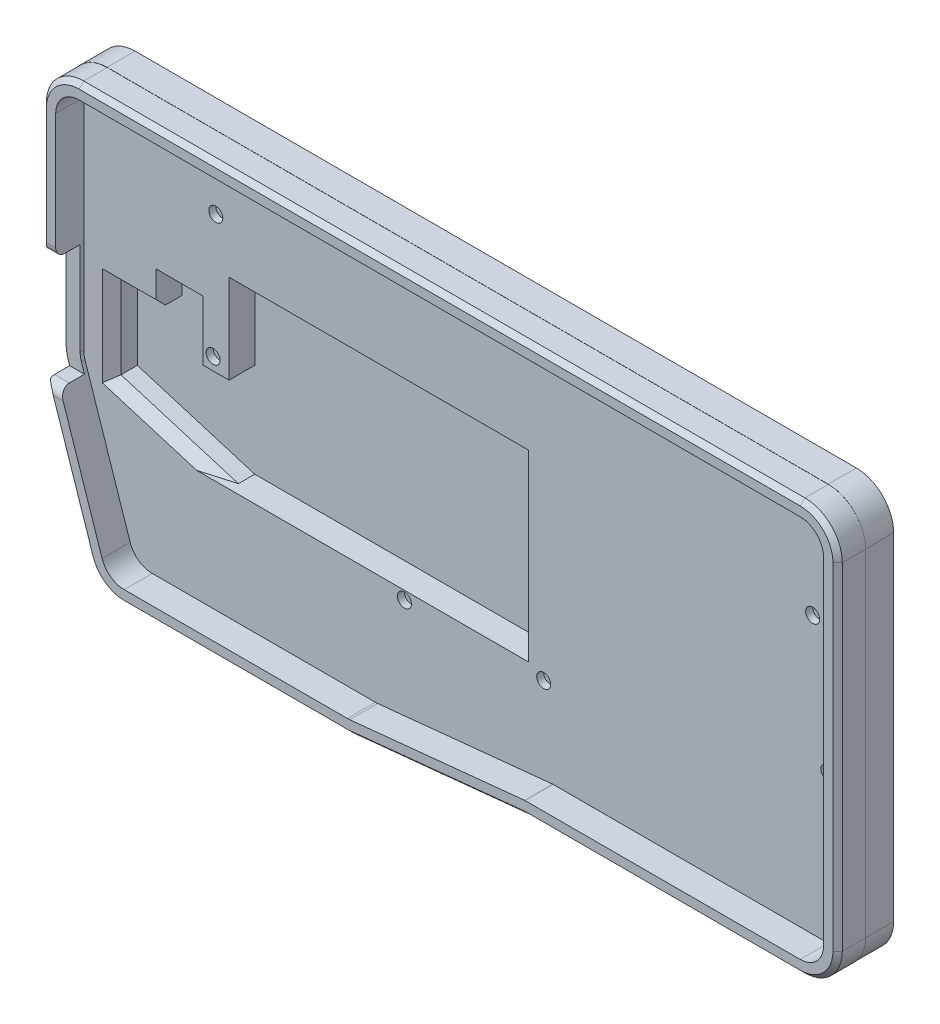
SolidWorks part; units mm, degrees
ref_plane "Front Plane" through (0, 0, 0) normal (0, 0, 1) x (1, 0, 0)
ref_plane "Top Plane" through (0, 0, 0) normal (0, 1, 0) x (1, 0, 0)
ref_plane "Right Plane" through (0, 0, 0) normal (1, 0, 0) x (0, 0, -1)
sketch "Sketch3" plane through (0, 0, 0) normal (0, 0, 1) x (1, 0, 0)
  line B0 (-83.6984, 57.4446) -> (70.5516, 57.3483)
  line B1 (78.5466, 49.3483) -> (78.5466, -22.6536)
  line B2 (70.5466, -30.6536) -> (11.7979, -30.6536)
  line B3 (11.7979, -30.6536) -> (-25.502, -34.4132)
  line B4 (-26.3043, -34.4536) -> (-74.0412, -34.4536)
  line B5 (-81.6306, -28.9834) -> (-91.2929, 0.0035)
  line B6 (-91.7034, 2.5333) -> (-91.7034, 49.4446)
  line B7 (-83.7003, 54.4446) -> (70.5497, 54.3483)
  line B8 (75.5466, 49.3483) -> (75.5466, -22.6536)
  line B9 (70.5466, -27.6536) -> (11.6974, -27.6536)
  line B10 (11.5971, -27.6586) -> (-25.8028, -31.4283)
  line B11 (-26.3043, -31.4536) -> (-74.0412, -31.4536)
  line B12 (-78.7846, -28.0347) -> (-88.4469, 0.9521)
  line B13 (-88.7034, 2.5333) -> (-88.7034, 49.4446)
  arc B14 (78.5466, 49.3483) -> (70.5516, 57.3483) centre (70.5466, 49.3483) ccw
  arc B15 (70.5466, -30.6536) -> (78.5466, -22.6536) centre (70.5466, -22.6536) ccw
  arc B16 (-26.3043, -34.4536) -> (-25.502, -34.4132) centre (-26.3043, -26.4536) ccw
  arc B17 (-81.6306, -28.9834) -> (-74.0412, -34.4536) centre (-74.0412, -26.4536) ccw
  arc B18 (-91.7034, 2.5333) -> (-91.2929, 0.0035) centre (-83.7034, 2.5333) ccw
  arc B19 (-83.6984, 57.4446) -> (-91.7034, 49.4446) centre (-83.7034, 49.4446) ccw
  arc B20 (75.5466, 49.3483) -> (70.5497, 54.3483) centre (70.5466, 49.3483) ccw
  arc B21 (70.5466, -27.6536) -> (75.5466, -22.6536) centre (70.5466, -22.6536) ccw
  arc B22 (11.6974, -27.6536) -> (11.5971, -27.6586) centre (11.6974, -28.6536) ccw
  arc B23 (-26.3043, -31.4536) -> (-25.8028, -31.4283) centre (-26.3043, -26.4536) ccw
  arc B24 (-78.7846, -28.0347) -> (-74.0412, -31.4536) centre (-74.0412, -26.4536) ccw
  arc B25 (-88.7034, 2.5333) -> (-88.4469, 0.9521) centre (-83.7034, 2.5333) ccw
  arc B26 (-83.7003, 54.4446) -> (-88.7034, 49.4446) centre (-83.7034, 49.4446) ccw
sketch_block_instance "wall_outline (2)-1"
sketch_block "wall_outline (2)"
extrude "Boss-Extrude1" add sketch "Sketch3" along normal blind 6
sketch "Sketch4" plane through (0, 0, 0) normal (0, 0, 1) x (1, 0, 0)
  line B0 (-83.7091, 57.4792) -> (70.5409, 57.3829)
  line B1 (78.5359, 49.3829) -> (78.5359, -22.619)
  line B2 (70.5359, -30.619) -> (11.7872, -30.619)
  line B3 (11.7872, -30.619) -> (-25.5126, -34.3786)
  line B4 (-26.3149, -34.419) -> (-74.0518, -34.419)
  line B5 (-81.6413, -28.9488) -> (-91.3036, 0.038)
  line B6 (-91.7141, 2.5679) -> (-91.7141, 49.4792)
  line B7 (-83.711, 54.4792) -> (70.539, 54.3829)
  line B8 (75.5359, 49.3829) -> (75.5359, -22.619)
  line B9 (70.5359, -27.619) -> (11.6867, -27.619)
  line B10 (11.5864, -27.624) -> (-25.8135, -31.3938)
  line B11 (-26.3149, -31.419) -> (-74.0518, -31.419)
  line B12 (-78.7953, -28.0001) -> (-88.4575, 0.9867)
  line B13 (-88.7141, 2.5679) -> (-88.7141, 49.4792)
  arc B14 (78.5359, 49.3829) -> (70.5409, 57.3829) centre (70.5359, 49.3829) ccw
  arc B15 (70.5359, -30.619) -> (78.5359, -22.619) centre (70.5359, -22.619) ccw
  arc B16 (-26.3149, -34.419) -> (-25.5126, -34.3786) centre (-26.3149, -26.419) ccw
  arc B17 (-81.6413, -28.9488) -> (-74.0518, -34.419) centre (-74.0518, -26.419) ccw
  arc B18 (-91.7141, 2.5679) -> (-91.3036, 0.038) centre (-83.7141, 2.5679) ccw
  arc B19 (-83.7091, 57.4792) -> (-91.7141, 49.4792) centre (-83.7141, 49.4792) ccw
  arc B20 (75.5359, 49.3829) -> (70.539, 54.3829) centre (70.5359, 49.3829) ccw
  arc B21 (70.5359, -27.619) -> (75.5359, -22.619) centre (70.5359, -22.619) ccw
  arc B22 (11.6867, -27.619) -> (11.5864, -27.624) centre (11.6867, -28.619) ccw
  arc B23 (-26.3149, -31.419) -> (-25.8135, -31.3938) centre (-26.3149, -26.419) ccw
  arc B24 (-78.7953, -28.0001) -> (-74.0518, -31.419) centre (-74.0518, -26.419) ccw
  arc B25 (-88.7141, 2.5679) -> (-88.4575, 0.9867) centre (-83.7141, 2.5679) ccw
  arc B26 (-83.711, 54.4792) -> (-88.7141, 49.4792) centre (-83.7141, 49.4792) ccw
  circle B27 centre (-60.4641, 41.881) radius 1
  circle B28 centre (-61.0341, 15.281) radius 1
  circle B29 centre (-20.1141, -9.419) radius 1
  circle B30 centre (9.6859, -9.419) radius 1
  circle B31 centre (70.4859, 3.881) radius 1
  circle B32 centre (67.2159, 31.431) radius 1
sketch_block_instance "wall_outline (3)-1"
sketch_block "wall_outline (3)"
extrude "Boss-Extrude2" add sketch "Sketch4" against normal blind 6 contours B7 B26 B13 B25 B12 B24 B11 B23 B10 B22 B9 B21 B8 B20 B32 B31 B30 B29 B28 B27 | B0 B19 B6 B18 B5 B17 B4 B16 B3 B2 B15 B1 B14 B26 B7 B20 B8 B21 B9 B22 B10 B23 B11 B24 B12 B25 B13 region at (-6.5853, 55.4963, 0) region at (-6.5032, 12.8796, 0)
sketch "Sketch5" plane through (0, 0, 0) normal (0, 0, 1) x (1, 0, 0)
  line L1 (-57.625, 35.0163) -> (6.3958, 35.0163)
  line L2 (-57.625, 35.0163) -> (-57.625, -7.6057)
  line L3 (-57.625, -7.6057) -> (6.3958, -7.6057)
  line L4 (6.3958, 35.0163) -> (6.3958, -7.6057)
  line L5 (-76.0419, 12.5652) -> (-50.0828, 12.5652)
  line L6 (-76.0419, 12.5652) -> (-76.0419, -1.6421)
  line L7 (-76.0419, -1.6421) -> (-50.0828, -1.6421)
  line L8 (-50.0828, 12.5652) -> (-50.0828, -1.6421)
extrude "Cut-Extrude2" cut sketch "Sketch5" against normal blind 5.5 contours L6 L7 L2 L5 | L8 L5 L2 L7 | L5 L8 L7 L2 L3 L4 L1 region at (-24.4603, 14.0423, 0) region at (-53.8539, 5.4615, 0) region at (-66.8334, 5.4615, 0)
sketch "Sketch6" plane through (0, 0, -6) normal (0, 0, -1) x (-1, 0, 0)
  circle A0 centre (-67.2159, 31.431) radius 1
  circle A1 centre (-70.4859, 3.881) radius 1
  circle A2 centre (-9.6859, -9.419) radius 1
  circle A3 centre (20.1141, -9.419) radius 1
  circle A4 centre (61.0341, 15.281) radius 1
  circle A5 centre (60.4641, 41.881) radius 1
extrude "Boss-Extrude3" add sketch "Sketch6" against normal blind 5.5
sketch "Sketch7" plane through (0, 0, 0) normal (0, 0, 1) x (1, 0, 0)
  circle A0 centre (-60.4641, 41.881) radius 1.5
  circle A1 centre (-61.0341, 15.281) radius 1.5
  circle A2 centre (-20.1141, -9.419) radius 1.5
  circle A3 centre (9.6859, -9.419) radius 1.5
  circle A7 centre (70.4859, 3.881) radius 1.5
  circle A8 centre (67.2159, 31.431) radius 1.5
extrude "Cut-Extrude3" cut sketch "Sketch7" against normal blind 1.5
sketch "Sketch8" plane through (0, 0, -6) normal (0, 0, -1) x (-1, 0, 0)
  line L0 (-70.5359, 49.3829) -> (-70.5359, -22.1639)
  line L1 (-70.5359, 49.3829) -> (83.7595, 49.3829)
  line L2 (-70.5359, -22.1639) -> (73.5863, -25.6718)
  circle A0 centre (-70.5359, 49.3829) radius 6
  circle A1 centre (-70.5359, -22.1639) radius 6
  circle A2 centre (83.7595, 49.3829) radius 6
  circle A3 centre (73.5863, -25.6718) radius 6
extrude "Cut-Extrude4" cut sketch "Sketch8" against normal blind 2.5 contours L1 A0 L0 | L0 A0 L1 | L0 A1 L2 | L2 A1 L0 | A3 | A2 region at (67.9894, 46.8364, -6) region at (71.3847, 50.2317, -6) region at (-73.6572, -19.842, -6) region at (67.9672, -19.657, -6) region at (71.4099, -23.0168, -6) region at (-83.7595, 55.2132, -6)
chamfer "Chamfer1" distance 1 angle 45 13 edges at (-78.7188, -32.9435, 6) (-86.4618, -14.49, 6) (-91.6001, 1.2518, 6) (-91.7034, 25.9889, 6) (-89.3585, 55.1032, 6) (-6.5734, 57.3964, 6) (76.2052, 55.0034, 6) (78.5466, 13.3474, 6) (76.2034, -28.3104, 6) (41.1722, -30.6536, 6) (-6.852, -32.5334, 6) (-25.9026, -34.4435, 6) (-50.1727, -34.4536, 6)
sketch "Sketch9" plane through (0.0358, 57.3923, 0) normal (0.0006, 1, 0) x (1, -0.0006, 0)
  line L1 (-81.193, -1.1526) -> (-62.3001, -1.1526)
  line L2 (-81.193, -1.1526) -> (-81.193, -7.0139)
  line L3 (-81.193, -7.0139) -> (-62.3001, -7.0139)
  line L4 (-62.3001, -1.1526) -> (-62.3001, -7.0139)
sketch "Sketch10" plane through (-91.7034, 0, 0) normal (-1, 0, 0) x (0, 0, 1)
  line L1 (0.7673, 22.5231) -> (7.4616, 22.5231)
  line L2 (0.7673, 22.5231) -> (0.7673, -1.0256)
  line L3 (0.7673, -1.0256) -> (7.4616, -1.0256)
  line L4 (7.4616, 22.5231) -> (7.4616, -1.0256)
  point P4 (7.4616, -1.0256)
extrude "Cut-Extrude6" cut sketch "Sketch10" against normal blind 5
fillet "Fillet2" radius 2 2 edges at (-88.8417, -1.0256, 6) (-89.7034, 22.5231, 6)
sketch "Sketch11" plane through (0, 0, 0) normal (0, 0, 1) x (1, 0, 0)
  line L1 (-73.2355, 25.3693) -> (-63.2377, 25.3693)
  line L2 (-73.2355, 25.3693) -> (-73.2355, 9.408)
  line L3 (-73.2355, 9.408) -> (-63.2377, 9.408)
  line L4 (-63.2377, 25.3693) -> (-63.2377, 9.408)
extrude "Cut-Extrude7" cut sketch "Sketch11" against normal blind 5.5
sketch "Sketch12" plane through (0, 0, -5.5) normal (0, 0, 1) x (1, 0, 0)
  line L0 (6.3958, 35.0163) -> (6.3958, -7.6057) construction
  line L1 (-57.625, 35.0163) -> (6.3958, 35.0163)
  line L2 (-57.625, 35.0163) -> (-57.625, 31.6402)
  line L3 (-57.625, 31.6402) -> (6.3958, 31.6402)
  line L4 (6.3958, 35.0163) -> (6.3958, 31.6402)
extrude "Boss-Extrude4" add sketch "Sketch12" along normal blind 5.5
sketch "Sketch13" plane through (0, 0, 0) normal (0, 0, 1) x (1, 0, 0)
  line L0 (-82.7449, 0) -> (-57.625, -7.6057)
  line L1 (-57.625, -7.6057) -> (-82.7449, 0)
  line L2 (-82.7449, 0) -> (-82.7449, 17.6789)
  line L3 (-82.7449, 17.6789) -> (-68.4274, 17.6789)
  line L4 (-68.4274, 17.6789) -> (-51.1131, -1.3002)
  line L5 (-51.1131, -1.3002) -> (-57.625, -7.6057)
  line M5 (-57.625, -7.6057) -> (-57.625, -1.6421)
  line M6 (-57.625, -1.6421) -> (-76.0419, -1.6421)
  line M7 (-76.0419, -1.6421) -> (-76.0419, 12.5652)
  line M8 (-76.0419, 12.5652) -> (-73.2355, 12.5652)
  line M9 (-73.2355, 12.5652) -> (-73.2355, 25.3693)
extrude "Cut-Extrude8" cut sketch "Sketch13" against normal blind 5.5 contours L3 L2 L0 M5 M6 M7 M8 M9 region at (-82.3885, 8.8394, 0)
chamfer "Chamfer2" distance 2 angle 45 1 edges at (-82.7449, 8.8394, 0)
chamfer "Chamfer3" distance 2 angle 45 1 edges at (-78.9902, 17.6789, 0)
chamfer "Chamfer4" distance 2 angle 45 1 edges at (-71.1849, -3.5001, 0)
